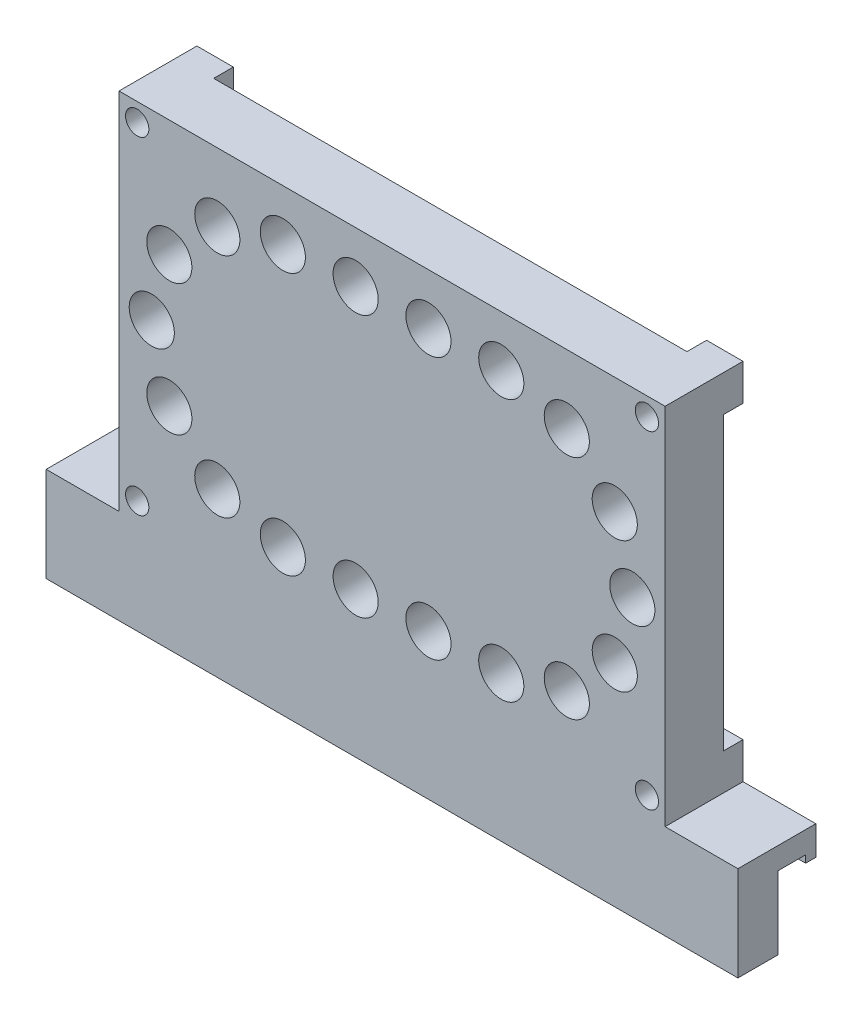
SolidWorks part; units mm, degrees
ref_plane "Front Plane" through (0, 0, 0) normal (0, 0, 1) x (1, 0, 0)
ref_plane "Top Plane" through (0, 0, 0) normal (0, 1, 0) x (1, 0, 0)
ref_plane "Right Plane" through (0, 0, 0) normal (1, 0, 0) x (0, 0, -1)
sketch "Esquisse1" plane through (0, 0, 0) normal (0, 0, 1) x (1, 0, 0)
  line L1 (-37.5, 25) -> (37.5, 25)
  line L2 (-37.5, 25) -> (-37.5, -25)
  line L3 (-37.5, -25) -> (37.5, -25)
  line L4 (37.5, 25) -> (37.5, -25)
  point P4 (-37.5, 0)
  point P6 (0, -25)
  dimension "D1" = 50
  dimension "D2" = 75
extrude "Main Extrusion" add sketch "Esquisse1" along normal blind 8
sketch "Esquisse2" plane through (0, 0, 8) normal (0, 0, 1) x (1, 0, 0)
  line L0 (-15, -8.2) -> (15, -8.2)
  line L1 (15, 8.2) -> (-15, 8.2)
  line L3 (-37.5, 25) -> (-37.5, -25) construction
  line L5 (-15, 2) -> (15, 2)
  line L6 (15, -2) -> (-15, -2)
  line L7 (37.5, 25) -> (-37.5, 25) construction
  arc A0 (15, -8.2) -> (15, 8.2) centre (15, 0) ccw
  arc A1 (15, -2) -> (15, 2) centre (15, 0) ccw
  arc A2 (-15, 2) -> (-15, -2) centre (-15, 0) ccw
  arc A3 (-15, 8.2) -> (-15, -8.2) centre (-15, 0) ccw
  point P17 (-37.5, 0)
  point P18 (0, 2)
  point P21 (0, 25)
  dimension "D3" = 2
  dimension "D2" = 8.2
  dimension "D6" = 30
extrude "Double Circle" cut sketch "Esquisse2" against normal blind 6
sketch "Esquisse3" plane through (0, 0, 8) normal (0, 0, 1) x (1, 0, 0)
  line L1 (-37.5, -20) -> (-32.5, -20)
  line L2 (-37.5, -20) -> (-37.5, -25)
  line L3 (-37.5, -25) -> (-32.5, -25)
  line L4 (-32.5, -20) -> (-32.5, -25)
  line L5 (-37.5, 25) -> (-32.5, 25)
  line L6 (-37.5, 25) -> (-37.5, 20)
  line L7 (-37.5, 20) -> (-32.5, 20)
  line L8 (-32.5, 25) -> (-32.5, 20)
  line L10 (37.5, 25) -> (32.5, 25)
  line L11 (37.5, 25) -> (37.5, 20)
  line L12 (37.5, 20) -> (32.5, 20)
  line L13 (32.5, 25) -> (32.5, 20)
  line L14 (37.5, -25) -> (32.5, -25)
  line L15 (37.5, -25) -> (37.5, -20)
  line L16 (37.5, -20) -> (32.5, -20)
  line L17 (32.5, -25) -> (32.5, -20)
  dimension "D1" = 5
  dimension "D2" = 5
  dimension "D3" = 5
extrude "Fixing Support" add sketch "Esquisse3" along normal blind 2.7
sketch "Esquisse4" plane through (0, 0, 10.7) normal (0, 0, 1) x (1, 0, 0)
  line L1 (-37.5, -20) -> (-37.5, -25) construction
  line L2 (-32.5, 8.2) -> (-32.5, 25) construction
  line L3 (-32.5, 25) -> (-37.5, 25) construction
  line L5 (37.5, -25) -> (37.5, -20) construction
  circle A0 centre (-35, -22.5) radius 1.6
  circle A1 centre (35, 22.5) radius 1.6
  circle A2 centre (-35, 22.5) radius 1.6
  circle A3 centre (35, -22.5) radius 1.6
  point P17 (-37.5, -22.5)
  dimension "D2" = 2.5
  dimension "D1" = 3.2
  dimension "D3" = 2.5
  dimension "D4" = 2.5
extrude "Fixing Hole" cut sketch "Esquisse4" against normal through all
sketch "Esquisse5" plane through (0, 0, 8) normal (0, 0, 1) x (1, 0, 0)
  circle A0 centre (-15, -18) radius 3.1
  arc A1 (-15, 2) -> (-15, -2) centre (-15, 0) ccw construction
  dimension "D1" = 6.2
  dimension "D2" = 18
extrude "Gear Linear Holes" cut sketch "Esquisse5" against normal through all
pattern_linear "Répétition linéaire1" count 3 spacing 10 along (1, 0, 0) of "Gear Linear Holes"
ref_plane "Plan1" through (15, 0, 0) normal (1, 0, 0) x (0, 0, -1)
ref_axis "Axe1" through (15, 0, -0.535) along (0, 0, 1)
sketch "Esquisse6" plane through (0, 0, 8) normal (0, 0, 1) x (1, 0, 0)
  line L0 (15, -5.885) -> (15, 5.885) construction
  line L2 (5.885, 0) -> (-5.885, 0) construction
  circle A0 centre (15, -18) radius 3.1
  dimension "D1" = 6.2
  dimension "D2" = 18
extrude "Gear Circle" cut sketch "Esquisse6" against normal through all
pattern_circular "Répétition circulaire1" count 7 every 30 about axis through (15, 0, -0.535) along (0, 0, 1) of "Gear Circle"
mirror "Symétrie2" about plane through (0, 0, 0) normal (1, 0, 0) of "Répétition circulaire1"
mirror "Symétrie3" about plane through (0, 0, 0) normal (0, 1, 0) of "Répétition linéaire1"
sketch "Esquisse8" plane through (0, 0, 0) normal (1, 0, 0) x (0, 0, -1)
  line L0 (-5.5, -28) -> (-5.5, -38)
  line L1 (-5.5, -28) -> (-9.3, -28)
  line L2 (-9.3, -28) -> (-9.3, -29)
  line L3 (-9.3, -29) -> (-10.7, -29)
  line L4 (-10.7, -29) -> (-10.7, -25)
  line L5 (-10.7, -25) -> (0, -25)
  line L6 (-5.5, -38) -> (0, -38)
  line L7 (0, -38) -> (0, -25)
  dimension "D1" = 1.4
  dimension "D2" = 5.2
  dimension "D3" = 1
  dimension "D4" = 3
  dimension "D5" = 10
extrude "Boss.-Extru.1" add sketch "Esquisse8" along normal mid plane 95
sketch "Esquisse9" [suppressed] plane through (0, -25, 0) normal (0, 1, 0) x (1, 0, 0)
  line L1 (-47.5, 0) -> (-47.5, -10.7) construction
  line L2 (-37.5, -10.7) -> (-47.5, -10.7) construction
  line L3 (47.5, -10.7) -> (37.5, -10.7) construction
  line L4 (47.5, 0) -> (47.5, -10.7) construction
  circle A0 centre (-42.5, -10.7) radius 1.6
  circle A1 centre (42.5, -10.7) radius 1.6
  dimension "D1" = 3.2
  dimension "D3" = 3.2
  dimension "D2" = 5
  dimension "D4" = 5
extrude "Enlèv. mat.-Extru.2" [suppressed] cut sketch "Esquisse9" against normal through all
sketch "Esquisse10" [suppressed] plane through (0, 0, 0) normal (0, 0, -1) x (-1, 0, 0)
  line L0 (47.5, -38) -> (47.5, -25) construction
  line L1 (-47.5, -38) -> (-47.5, -25) construction
  line L2 (-47.5, -38) -> (47.5, -38) construction
  circle A0 centre (-42.5, -33) radius 1.6
  circle A1 centre (42.5, -33) radius 1.6
  dimension "D2" = 3.2
  dimension "D1" = 5
  dimension "D3" = 5
  dimension "D4" = 5
extrude "Enlèv. mat.-Extru.3" [suppressed] cut sketch "Esquisse10" against normal up to surface (5.5 mm away) up to face at (0, -33, 5.5)
mirror "Symétrie4" about plane through (0, 0, 10.7) normal (0, 0, 1) of bodies 113 111
sketch "Esquisse7" plane through (-37.5, 0, 0) normal (-1, 0, 0) x (0, 0, 1)
  line L1 (10.7, 45) -> (-29.3, 45)
  line L2 (10.7, 45) -> (10.7, -55)
  line L3 (10.7, -55) -> (-29.3, -55)
  line L4 (-29.3, 45) -> (-29.3, -55)
  line L5 (10.7, 25) -> (10.7, 20) construction
  line L6 (10.7, 25) -> (0, 25) construction
  point P4 (-44.2174, -43.9826)
  dimension "D1" = 20
  dimension "D2" = 100
  dimension "D3" = 40
extrude "Enlèv. mat.-Extru.1" cut sketch "Esquisse7" against normal through all both and the other way through all
